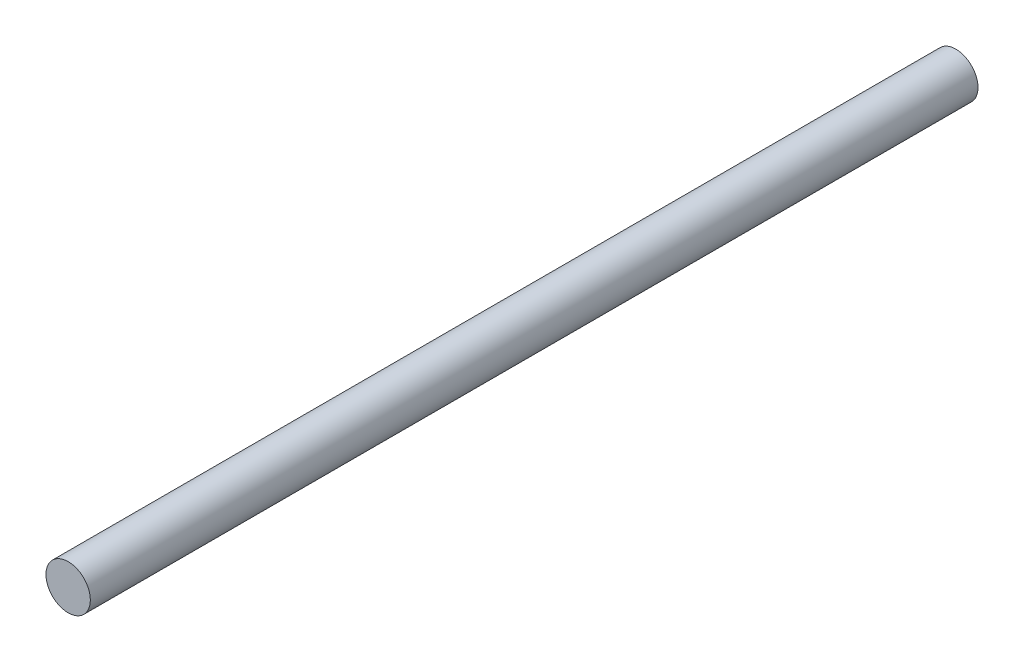
SolidWorks part; units mm, degrees
material "Plain Carbon Steel"
ref_plane "Front Plane" through (0, 0, 0) normal (0, 0, 1) x (1, 0, 0)
ref_plane "Top Plane" through (0, 0, 0) normal (0, 1, 0) x (1, 0, 0)
ref_plane "Right Plane" through (0, 0, 0) normal (1, 0, 0) x (0, 0, -1)
sketch "Sketch1" plane through (0, 0, 0) normal (0, 0, 1) x (1, 0, 0)
  circle A0 centre (0, 0) radius 10
  dimension "Diameter" = 20
extrude "Shaft Extrude" add sketch "Sketch1" along normal blind 400 contours A0
equation "\"Diameter@Sketch1\"=\"ShaftDiameter\""
equation "\"ExtrusionStandard\"= 20mm'Size of extrusion used for framing"
equation "\"BaseExtrusionFrameWidth\"= 60mm"
equation "\"BaseExtrusionFrameHeight\"= 20mm"
equation "\"PlateThickness\"= 15mm"
equation "\"RailHeight\"=13"
equation "\"WallThickness\"= 3mm"
equation "\"ShaftDiameter\"= 20mm"
equation "\"ShaftClearance\"= 1mm"
equation "\"PlainBearingBoltCircleDiameter\" = ( \"WallThickness\" + \"M3_ClearanceDiameter\" / 2 ) * 2 + \"PlainBearingOD\""
equation "\"PlainBearingBoltcount\"=5"
equation "\"ThrustBearingOD\"= 35mm"
equation "\"ThrustBearingID\"= 20mm"
equation "\"ThrustBearingThickness\"= 10mm"
equation "\"RearCollarOD\"= 32mm"
equation "\"RearCollarID\"= 20mm"
equation "\"RearCollarThickness\"= 14mm"
equation "\"LeadScrewDiameter\"= 6.35mm"
equation "\"LeadScrewHeight\"= 10mm'Height of Lead screw from bottom of gantry extrusion"
equation "\"LeadScrewNut_FlangeOD\"= 25mm'OD of the lead screw nut flange"
equation "\"LeadScrewNut_BoltCircleDiameter\"= 19mm"
equation "\"LeadScrewNut_BoltCount\"= 6"
equation "\"ShaftOffset_BaseThickness\"= 6mm + \"WallThickness\""
equation "\"PillowHeight\"= \"ShaftOffset_BaseThickness\" + \"ExtrusionStandard\""
equation "\"X_BeltPitch\"= 2mm"
equation "\"X_Drive_Teeth\"= 20"
equation "\"X_Shaft_Teeth\"= 60"
equation "\"X_Drive_PD\"= ( \"X_Drive_Teeth\" * \"X_BeltPitch\" ) / PI"
equation "\"X_Shaft_PD\"= ( \"X_Shaft_Teeth\" * \"X_BeltPitch\" ) / PI"
equation "\"X_CenterDistance\"= 55mm"
equation "\"GantryLength\"= 150mm'Length of the gantry extrusion/plate"
equation "\"X_MotorPlateThickness\"= 15mm"
equation "\"X_MotorPlateLength\"= \"X_MotorPlateThickness\" + \"ExtrusionStandard\" * 2"
equation "\"X_BeltWidth\"= 10mm"
equation "\"X_PillowLength\"= ( \"WallThickness\" * 4 ) + \"RearCollarThickness\" + ( \"ThrustBearingThickness\" * 2 ) + \"ShaftRotaryBearingThickness\""
equation "\"ShaftRotaryBearingThickness\" = 9mm"
equation "\"ShaftRotaryBearingOD\"= 37mm"
equation "\"ShaftLength\"= 400mm'Length of the main shaft.\\"
equation "\"D1@Shaft Extrude\"=\"ShaftLength\""
